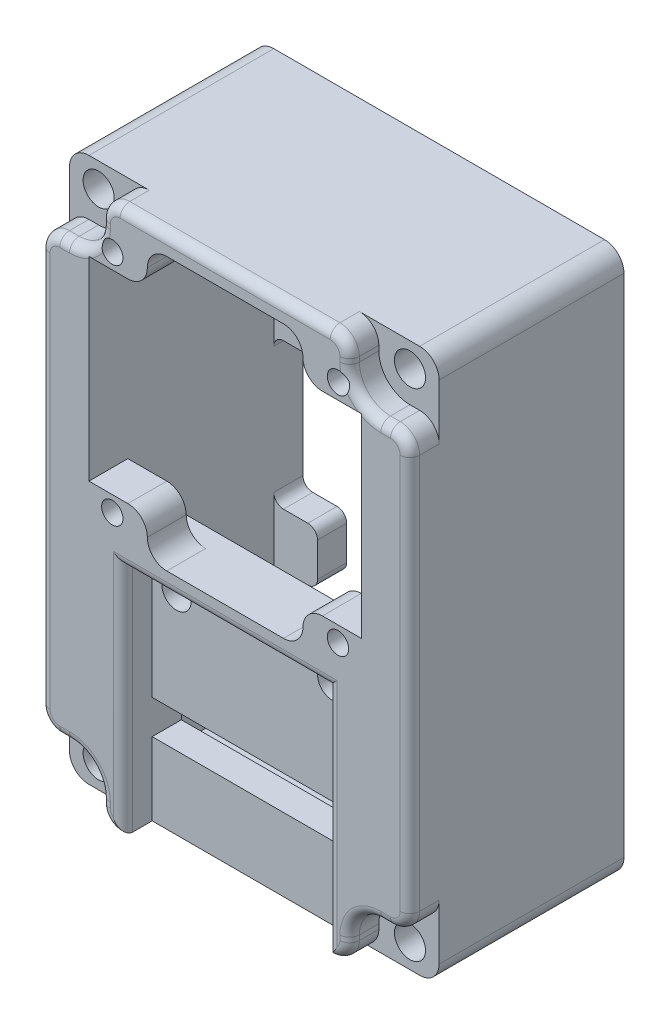
SolidWorks part; units mm, degrees
ref_plane "前视基准面" through (0, 0, 0) normal (0, 0, 1) x (1, 0, 0)
ref_plane "上视基准面" through (0, 0, 0) normal (0, 1, 0) x (1, 0, 0)
ref_plane "右视基准面" through (0, 0, 0) normal (1, 0, 0) x (0, 0, -1)
sketch "草图1" plane through (0, 0, 0) normal (0, 0, 1) x (1, 0, 0)
  line L1 (-19, 16) -> (19, 16)
  line L2 (-19, 16) -> (-19, -40)
  line L3 (-19, -40) -> (19, -40)
  line L4 (19, 16) -> (19, -40)
  line L5 (-19, 16) -> (19, -40) construction
  line L6 (-19, -40) -> (19, 16) construction
  point P0 (0, -12)
  dimension "D1" = 56
  dimension "D2" = 38
  dimension "D3" = 12
extrude "凸台-拉伸1" add sketch "草图1" along normal blind 22
sketch "草图2" plane through (0, 0, 22) normal (0, 0, 1) x (1, 0, 0)
  line L1 (-14, -10) -> (14, -10)
  line L2 (-14, -10) -> (-14, 10)
  line L3 (-14, 10) -> (14, 10)
  line L4 (14, -10) -> (14, 10)
  line L5 (-14, -10) -> (14, 10) construction
  line L6 (-14, 10) -> (14, -10) construction
  point P0 (0, 0)
  dimension "D1" = 20
  dimension "D2" = 28
extrude "切除-拉伸1" cut sketch "草图2" against normal through all
sketch "草图5" plane through (0, 0, 22) normal (0, 0, 1) x (1, 0, 0)
  line L0 (-14, -10) -> (14, -10) construction
  line L1 (-10.5, -16) -> (10.5, -16)
  line L2 (-10.5, -16) -> (-10.5, -32)
  line L3 (-10.5, -32) -> (10.5, -32)
  line L4 (10.5, -16) -> (10.5, -32)
  line L5 (-10.5, -16) -> (10.5, -32) construction
  line L6 (-10.5, -32) -> (10.5, -16) construction
  point P0 (0, -24)
  dimension "D1" = 21
  dimension "D2" = 16
  dimension "D3" = 6
extrude "切除-拉伸4" cut sketch "草图5" against normal blind 3
sketch "草图6" plane through (0, 0, 19) normal (0, 0, 1) x (1, 0, 0)
  line L0 (10.5, -16) -> (-10.5, -16) construction
  line L1 (-10.5, -29) -> (10.5, -29)
  line L2 (-10.5, -29) -> (-10.5, -32.5)
  line L3 (-10.5, -32.5) -> (10.5, -32.5)
  line L4 (10.5, -29) -> (10.5, -32.5)
  line L5 (-10.5, -29) -> (10.5, -32.5) construction
  line L6 (-10.5, -32.5) -> (10.5, -29) construction
  point P0 (0, -30.75)
  point P6 (0, -27.1619)
  dimension "D1" = 3.5
  dimension "D2" = 21
  dimension "D3" = 13
extrude "切除-拉伸5" cut sketch "草图6" against normal through all
sketch "草图7" plane through (0, 0, 0) normal (0, 0, -1) x (-1, 0, 0)
  line L1 (-14, -14) -> (14, -14)
  line L2 (-14, -14) -> (-14, 14)
  line L3 (-14, 14) -> (14, 14)
  line L4 (14, -14) -> (14, 14)
  line L5 (-14, -14) -> (14, 14) construction
  line L6 (-14, 14) -> (14, -14) construction
  point P0 (0, 0)
  dimension "D1" = 28
  dimension "D2" = 28
extrude "切除-拉伸6" cut sketch "草图7" against normal blind 18
sketch "草图8" plane through (0, 0, 22) normal (0, 0, 1) x (1, 0, 0)
  line L1 (19, 16) -> (-19, 16) construction
  line L2 (0, 16) -> (0, -40) construction
  line L3 (-19, -40) -> (19, -40) construction
  line L4 (-19, -12) -> (19, -12) construction
  line L5 (-19, 16) -> (-19, -40) construction
  line L6 (19, -40) -> (19, 16) construction
  circle A0 centre (-16, 13.5) radius 1.6
  circle A1 centre (16, 13.5) radius 1.6
  circle A2 centre (16, -37.5) radius 1.6
  circle A3 centre (-16, -37.5) radius 1.6
  dimension "D1" = 3
  dimension "D2" = 3.2
  dimension "D3" = 2.5
extrude "切除-拉伸7" cut sketch "草图8" against normal through all
sketch "草图9" plane through (0, 0, 18) normal (0, 0, -1) x (-1, 0, 0)
  line L1 (11.6, -11.6) -> (-11.6, -11.6) construction
  line L2 (11.6, -11.6) -> (11.6, 11.6) construction
  line L3 (11.6, 11.6) -> (-11.6, 11.6) construction
  line L4 (-11.6, -11.6) -> (-11.6, 11.6) construction
  line L5 (11.6, -11.6) -> (-11.6, 11.6) construction
  line L6 (11.6, 11.6) -> (-11.6, -11.6) construction
  circle A0 centre (-11.6, 11.6) radius 1.1
  circle A1 centre (11.6, 11.6) radius 1.1
  circle A2 centre (11.6, -11.6) radius 1.1
  circle A3 centre (-11.6, -11.6) radius 1.1
  point P0 (0, 0)
  dimension "D3" = 2.2
  dimension "D4" = 2.2
  dimension "D5" = 2.2
  dimension "D6" = 2.2
  dimension "D1" = 23.2
  dimension "D2" = 23.2
extrude "切除-拉伸8" cut sketch "草图9" against normal through all
sketch "草图10" plane through (0, 0, 22) normal (0, 0, 1) x (1, 0, 0)
  line L1 (-8, -14) -> (8, -14)
  line L2 (-8, -14) -> (-8, 14)
  line L3 (-8, 14) -> (8, 14)
  line L4 (8, -14) -> (8, 14)
  line L5 (-8, -14) -> (8, 14) construction
  line L6 (-8, 14) -> (8, -14) construction
  point P0 (0, 0)
  dimension "D1" = 16
  dimension "D2" = 28
extrude "切除-拉伸9" cut sketch "草图10" against normal through all
sketch "草图11" plane through (0, 0, 19) normal (0, 0, 1) x (1, 0, 0)
  line L0 (0, 0) -> (0, -40) construction
  line L1 (-19, -40) -> (19, -40) construction
  line L2 (10.5, -16) -> (-10.5, -16) construction
  circle A0 centre (-8, -18.5) radius 1.5
  circle A1 centre (8, -18.5) radius 1.5
  dimension "D1" = 2.5
  dimension "D2" = 3
  dimension "D3" = 8
extrude "切除-拉伸10" cut sketch "草图11" against normal through all
fillet "圆角1" radius 2 8 edges at (-8, 10, 20) (8, 10, 20) (-8, -10, 20) (-8, -14, 20) (8, -10, 20) (8, -14, 20) (-8, 14, 20) (8, 14, 20)
fillet "圆角2" radius 2 4 edges at (19, -40, 11) (-19, -40, 11) (19, 16, 11) (-19, 16, 11)
sketch "草图12" plane through (0, 0, 0) normal (0, 0, -1) x (-1, 0, 0)
  line L1 (-14, -38) -> (14, -38)
  line L2 (-14, -38) -> (-14, -14)
  line L3 (-14, -14) -> (14, -14)
  line L4 (14, -38) -> (14, -14)
  line L5 (-14, -38) -> (14, -14) construction
  line L6 (-14, -14) -> (14, -38) construction
  line L7 (-14, -14) -> (-6, -14) construction
  point P0 (0, -26)
  point P7 (0, 0)
  dimension "D1" = 28
  dimension "D2" = 24
extrude "切除-拉伸11" cut sketch "草图12" against normal blind 16
sketch "草图13" plane through (0, 0, 22) normal (0, 0, 1) x (1, 0, 0)
  line L0 (10.5, -32) -> (10.5, -16) construction
  line L1 (-10.5, -40.4558) -> (10.5, -40.4558)
  line L2 (-10.5, -40.4558) -> (-10.5, -32)
  line L3 (-10.5, -32) -> (10.5, -32)
  line L4 (10.5, -40.4558) -> (10.5, -32)
  line L5 (-10.5, -40.4558) -> (10.5, -32) construction
  line L6 (-10.5, -32) -> (10.5, -40.4558) construction
  line L7 (-10.5, -32) -> (10.5, -32) construction
  point P0 (0, -36.2279)
extrude "切除-拉伸12" cut sketch "草图13" against normal up to surface (3 mm away) up to face at (-6.5, -18.5, 19)
sketch "草图14" plane through (0, -40, 0) normal (0, -1, 0) x (-1, 0, 0)
  line L0 (17, 0) -> (-17, 0) construction
  line L1 (6, -4) -> (-6, -4)
  line L2 (6, -4) -> (6, 0)
  line L3 (6, 0) -> (-6, 0)
  line L4 (-6, -4) -> (-6, 0)
  line L5 (6, -4) -> (-6, 0) construction
  line L6 (6, 0) -> (-6, -4) construction
  point P0 (0, -2)
  point P7 (0, 0)
  dimension "D1" = 12
  dimension "D2" = 4
extrude "切除-拉伸13" cut sketch "草图14" against normal up to next
sketch "草图15" plane through (0, 0, 22) normal (0, 0, 1) x (1, 0, 0)
  line L0 (-12.8, 13.5) -> (-12.8, 16)
  line L1 (17, 16) -> (-17, 16) construction
  line L2 (-12.8, 16) -> (-17, 16)
  line L3 (-16, 10.3) -> (-19, 10.3)
  line L4 (-19, 14) -> (-19, -38) construction
  line L5 (-19, 10.3) -> (-19, 14)
  line L6 (0, 16) -> (0, -40) construction
  line L7 (-10.5, -40) -> (10.5, -40) construction
  line L8 (-19, -12) -> (19, -12) construction
  line L9 (19, -38) -> (19, 14) construction
  line L10 (12.8, 13.5) -> (12.8, 16)
  line L11 (12.8, 16) -> (17, 16)
  line L12 (19, 10.3) -> (19, 14)
  line L13 (16, 10.3) -> (19, 10.3)
  line L14 (16, -34.3) -> (19, -34.3)
  line L15 (19, -34.3) -> (19, -38)
  line L16 (12.8, -40) -> (17, -40)
  line L17 (12.8, -37.5) -> (12.8, -40)
  line L18 (-12.8, -37.5) -> (-12.8, -40)
  line L19 (-12.8, -40) -> (-17, -40)
  line L20 (-19, -34.3) -> (-19, -38)
  line L21 (-16, -34.3) -> (-19, -34.3)
  arc A0 (-16, 10.3) -> (-12.8, 13.5) centre (-16, 13.5) ccw
  arc A1 (-17, 16) -> (-19, 14) centre (-17, 14) ccw construction
  arc A2 (-17, 16) -> (-19, 14) centre (-17, 14) ccw
  arc A3 (16, 10.3) -> (12.8, 13.5) centre (16, 13.5) cw
  arc A4 (17, 16) -> (19, 14) centre (17, 14) cw
  arc A5 (17, -40) -> (19, -38) centre (17, -38) ccw
  arc A6 (16, -34.3) -> (12.8, -37.5) centre (16, -37.5) ccw
  arc A7 (-16, -34.3) -> (-12.8, -37.5) centre (-16, -37.5) cw
  arc A8 (-17, -40) -> (-19, -38) centre (-17, -38) cw
  dimension "D1" = 6.4
extrude "切除-拉伸14" cut sketch "草图15" against normal blind 3
fillet "圆角4" radius 2 8 edges at (19, -34.3, 20.5) (12.8, -40, 20.5) (-19, -34.3, 20.5) (-12.8, -40, 20.5) (-19, 10.3, 20.5) (-12.8, 16, 20.5) (12.8, 16, 20.5) (19, 10.3, 20.5)
fillet "圆角5" radius 1 26 edges at (12.2142, -39.4142, 22) (12.8, -37.75, 22) (13.7373, -35.2373, 22) (16.5, -34.3, 22) (18.4142, -33.7142, 22) (19, -12, 22) (18.4142, 9.7142, 22) (16.5, 10.3, 22) (13.7373, 11.2373, 22) (12.8, 13.75, 22) (12.2142, 15.4142, 22) (0, 16, 22) (-12.2142, 15.4142, 22) (-12.8, 13.75, 22) (-13.7373, 11.2373, 22) (-16.5, 10.3, 22) (-18.4142, 9.7142, 22) (-12.2142, -39.4142, 22) (-12.8, -37.75, 22) (-13.7373, -35.2373, 22) (-16.5, -34.3, 22) (-18.4142, -33.7142, 22) (10.5, -28, 22) (0, -16, 22) (-10.5, -28, 22) (-19, -12, 22)
sketch "草图16" plane through (0, 0, 0) normal (0, 0, -1) x (-1, 0, 0)
  line L1 (-9.5, -27) -> (-14, -27)
  line L2 (-9.5, -27) -> (-9.5, 3)
  line L3 (-9.5, 3) -> (-14, 3)
  line L4 (-14, -27) -> (-14, 3)
  line L5 (-9.5, -27) -> (-14, 3) construction
  line L6 (-9.5, 3) -> (-14, -27) construction
  line L7 (0, 16) -> (0, -40) construction
  line L8 (-17, 16) -> (17, 16) construction
  line L9 (-6, -40) -> (6, -40) construction
  line L10 (9.5, 3) -> (14, 3)
  line L11 (14, -27) -> (14, 3)
  line L12 (9.5, -27) -> (14, -27)
  line L13 (9.5, -27) -> (9.5, 3)
  line L14 (-14, -38) -> (-14, 14) construction
  point P0 (-11.75, -12)
  point P6 (-5.637, 1.8861)
  point P7 (-11.2016, -11.9063)
  point P21 (-9.0366, -12)
  dimension "D1" = 28
  dimension "D2" = 30
  dimension "D3" = 4.5
extrude "凸台-拉伸2" add sketch "草图16" against normal blind 3
sketch "草图17" plane through (0, 0, 0) normal (0, 0, -1) x (-1, 0, 0)
  line L0 (14, -14) -> (-14, -14) construction
  line L1 (-14, -21.5) -> (14, -21.5)
  line L2 (-14, -21.5) -> (-14, -6.5)
  line L3 (-14, -6.5) -> (14, -6.5)
  line L4 (14, -21.5) -> (14, -6.5)
  line L5 (-14, -21.5) -> (14, -6.5) construction
  line L6 (-14, -6.5) -> (14, -21.5) construction
  point P0 (0, -14)
  dimension "D1" = 28
  dimension "D2" = 15
extrude "切除-拉伸15" cut sketch "草图17" against normal blind 3
fillet "圆角6" radius 1 16 edges at (9.5, 3, 1.5) (14, 3, 1.5) (14, -21.5, 1.5) (9.5, -6.5, 1.5) (14, -6.5, 1.5) (9.5, -21.5, 1.5) (9.5, -27, 1.5) (14, -27, 1.5) (-9.5, -21.5, 1.5) (-9.5, -27, 1.5) (-14, -27, 1.5) (-9.5, -6.5, 1.5) (-9.5, 3, 1.5) (-14, 3, 1.5) (-14, -21.5, 1.5) (-14, -6.5, 1.5)
